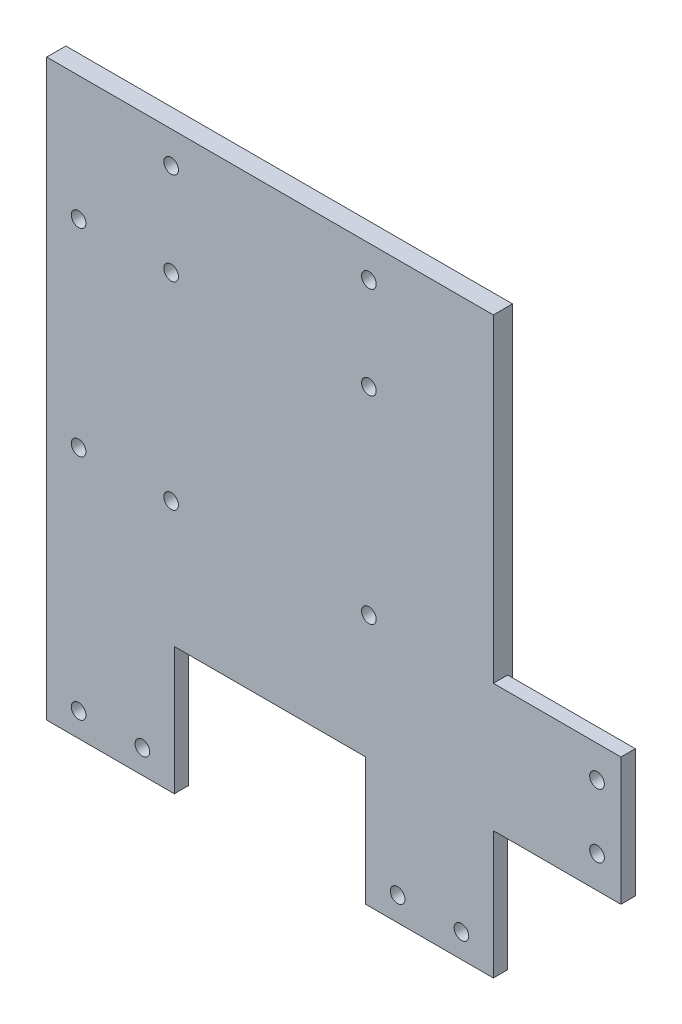
SolidWorks part; units mm, degrees
ref_plane "Front Plane" through (0, 0, 0) normal (0, 0, 1) x (1, 0, 0)
ref_plane "Top Plane" through (0, 0, 0) normal (0, 1, 0) x (1, 0, 0)
ref_plane "Right Plane" through (0, 0, 0) normal (1, 0, 0) x (0, 0, -1)
sketch "Sketch1" plane through (0, 0, -16.6) normal (0, 0, -1) x (1, 0, 0)
  line L0 (-31, -70) -> (-31, -60) construction
  line L1 (-70, -70) -> (70, -70)
  line L2 (-70, -70) -> (-70, 70)
  line L3 (-70, 70) -> (70, 70)
  line L4 (70, -70) -> (70, 70)
  line L5 (-70, -70) -> (70, 70) construction
  line L6 (-70, 70) -> (70, -70) construction
  line L7 (-70, -70) -> (70, -70) construction
  line L11 (0, -55) -> (0, 55) construction
  circle A0 centre (-31, -31) radius 2.3
  circle A1 centre (-31, 31) radius 2.3
  circle A2 centre (31, 31) radius 2.3
  circle A3 centre (31, -31) radius 2.3
  circle A4 centre (-31, -60) radius 2.3
  circle A5 centre (31, -60) radius 2.3
  circle A6 centre (-60, 31) radius 2.3
  circle A7 centre (-60, -31) radius 2.3
  point P0 (0, 0)
  point P18 (0, 0)
  point P30 (0, 0)
  dimension "D1" = 2
extrude "Boss-Extrude1" add sketch "Sketch1" along normal blind 6
sketch "Sketch2" plane through (0, 0, -16.6) normal (0, 0, 1) x (1, 0, 0)
  line L0 (30, -70) -> (70, -70)
  line L1 (0, -55) -> (0, 55) construction
  line L4 (70, -110) -> (30, -110)
  line L5 (30, -70) -> (30, -110)
  line L7 (70, -70) -> (70, -30)
  line L8 (70, -30) -> (110, -30)
  line L9 (110, -70) -> (110, -30)
  line L10 (70, -110) -> (70, -70)
  line L11 (70, -70) -> (110, -70)
  line L12 (50, -110) -> (50, -102.5) construction
  line L13 (50, -102.5) -> (30, -102.5) construction
  line L14 (50, -102.5) -> (50, -50) construction
  line L15 (110, -50) -> (50, -50) construction
  line L16 (-30, -70) -> (-70, -70)
  line L17 (-30, -70) -> (-30, -110)
  line L18 (-70, -110) -> (-30, -110)
  line L19 (-70, -110) -> (-70, -70)
  circle A0 centre (40, -102.5) radius 2.3
  circle A1 centre (60, -102.5) radius 2.3
  circle A2 centre (102.5, -60) radius 2.3
  circle A3 centre (102.5, -40) radius 2.3
  circle A4 centre (-60, -102.5) radius 2.3
  circle A5 centre (-40, -102.5) radius 2.3
  line M10 (-70, -70) -> (70, -70)
  dimension "D1" = 2
extrude "Boss-Extrude2" add sketch "Sketch2" against normal blind 4.5 contours A0 | A1 | L19 L18 L17 A4 A5 M10 | L10 L4 L5 L0 | L11 L9 L8 L7 | A2 | A3 region at (-50, -89.7348, -16.6) region at (40, -102.5, -16.6) region at (60, -102.5, -16.6)
